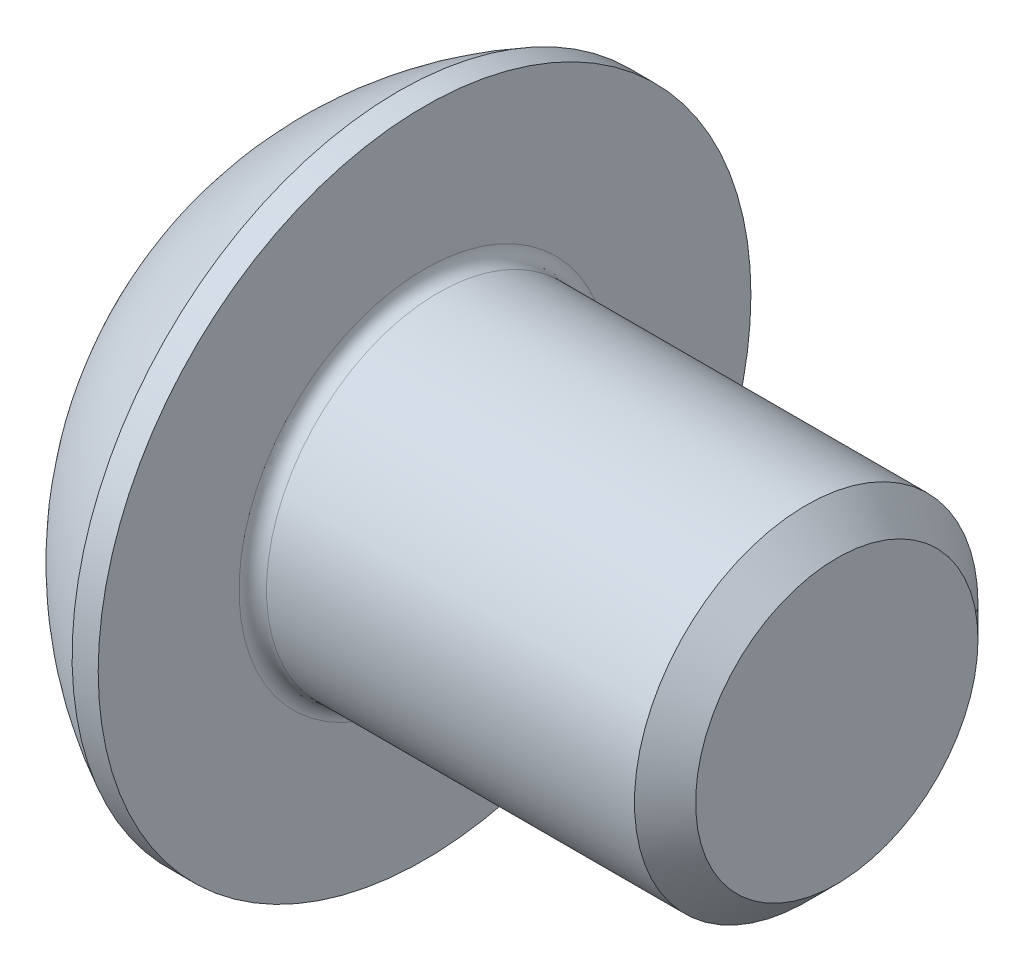
SolidWorks part; units mm, degrees
material "AISI 316 Stainless Steel Sheet (SS)"
ref_plane "Спереди" through (0, 0, 0) normal (0, 0, 1) x (1, 0, 0)
ref_plane "Сверху" through (0, 0, 0) normal (0, 1, 0) x (1, 0, 0)
ref_plane "Справа" through (0, 0, 0) normal (1, 0, 0) x (0, 0, -1)
sketch "Эскиз1" plane through (0, 0, 0) normal (0, 0, 1) x (1, 0, 0)
  line L0 (-3.6435, 0) -> (-10.508, 0) construction
  line L1 (0, 2.375) -> (0, 0)
  line L2 (0, 0) -> (8.75, 0)
  line L3 (8.75, 0) -> (8.75, 2.055)
  line L4 (8.75, 2.055) -> (8.305, 2.5)
  line L5 (8.305, 2.5) -> (2.75, 2.5)
  line L6 (2.75, 2.5) -> (2.75, 4.75)
  line L7 (2.75, 4.75) -> (2.3702, 4.75)
  arc A0 (2.3702, 4.75) -> (0, 2.375) centre (4.7549, 0) ccw
  dimension "D1" = 10.63
  dimension "D2" = 4.75
  dimension "D3" = 2.75
  dimension "D4" = 5
  dimension "D5" = 45
  dimension "D6" = 4.11
  dimension "D7" = 6
  dimension "D8" = 9.5
revolve "Body" add sketch "Эскиз1" angle 360 about L0
fillet "Скругление1" radius 0.2 1 edges at (2.75, 0, -2.5)
sketch "Эскиз2" plane through (0, 0, 0) normal (0, 0, 1) x (1, 0, 0)
  line L0 (0, 0) -> (0, 1.5)
  line L1 (0, 2.375) -> (0, -2.375) construction
  line L2 (0, 1.5) -> (1.56, 1.5)
  line L3 (1.56, 1.5) -> (2.426, 0)
  line L4 (2.426, 0) -> (0, 0)
  dimension "D1" = 1.56
  dimension "D2" = 60
  dimension "D3" = 1.5
revolve "Вырез-Повернуть1" cut sketch "Эскиз2" angle 360 about L4
sketch "Эскиз3" plane through (0, 0, 0) normal (-1, 0, 0) x (0, 0, 1)
  line L1 (-1.5, -0.866) -> (0, -1.7321)
  line L2 (0, -1.7321) -> (1.5, -0.866)
  line L3 (1.5, -0.866) -> (1.5, 0.866)
  line L4 (1.5, 0.866) -> (0, 1.7321)
  line L5 (0, 1.7321) -> (-1.5, 0.866)
  line L6 (-1.5, 0.866) -> (-1.5, -0.866)
  circle A0 centre (0, 0) radius 1.5 construction
  dimension "D1" = 3
extrude "Hex" cut sketch "Эскиз3" against normal blind 1.56
